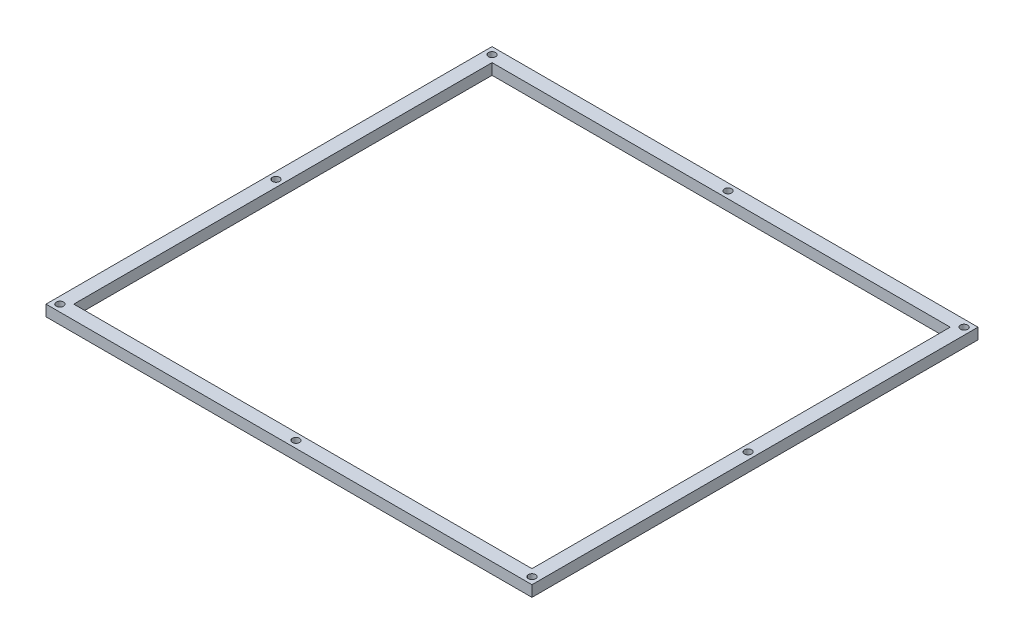
SolidWorks part; units mm, degrees
ref_plane "Front Plane" through (0, 0, 0) normal (0, 0, 1) x (1, 0, 0)
ref_plane "Top Plane" through (0, 0, 0) normal (0, 1, 0) x (1, 0, 0)
ref_plane "Right Plane" through (0, 0, 0) normal (1, 0, 0) x (0, 0, -1)
sketch "Sketch1" plane through (0, 0, 0) normal (0, 1, 0) x (1, 0, 0)
  line L0 (8, 249) -> (272, 249)
  line L1 (0, 0) -> (280, 0)
  line L2 (0, 0) -> (0, 257)
  line L3 (0, 257) -> (280, 257)
  line L4 (280, 0) -> (280, 257)
  line L5 (272, 8) -> (272, 249)
  line L6 (8, 8) -> (272, 8)
  line L7 (8, 8) -> (8, 249)
  line L8 (140, 257) -> (140, 249) construction
  dimension "D1" = 257
  dimension "D2" = 280
  dimension "D3" = 8
extrude "Boss-Extrude1" add sketch "Sketch1" along normal blind 6.35
sketch "Sketch2" plane through (0, 6.35, 0) normal (0, 1, 0) x (1, 0, 0)
  line L0 (0, 257) -> (8, 249) construction
  line L1 (0, 0) -> (8, 8) construction
  line L2 (272, 249) -> (280, 257) construction
  line L3 (272, 8) -> (280, 0) construction
  line L4 (4, 253) -> (4, 4) construction
  line L5 (4, 4) -> (276, 4) construction
  line L6 (276, 4) -> (276, 253) construction
  line L7 (276, 253) -> (4, 253) construction
  circle A0 centre (4, 253) radius 2.1
  circle A1 centre (4, 4) radius 2.1
  circle A2 centre (276, 253) radius 2.1
  circle A3 centre (276, 4) radius 2.1
  circle A4 centre (140, 253) radius 2.1
  circle A5 centre (4, 128.5) radius 2.1
  circle A6 centre (140, 4) radius 2.1
  circle A7 centre (276, 128.5) radius 2.1
  dimension "D1" = 4.2
  dimension "D2" = 4.2
  dimension "D3" = 4.2
  dimension "D4" = 4.2
  dimension "D5" = 4.2
  dimension "D6" = 4.2
  dimension "D7" = 4.2
  dimension "D8" = 4.2
extrude "Cut-Extrude1" cut sketch "Sketch2" against normal through all
